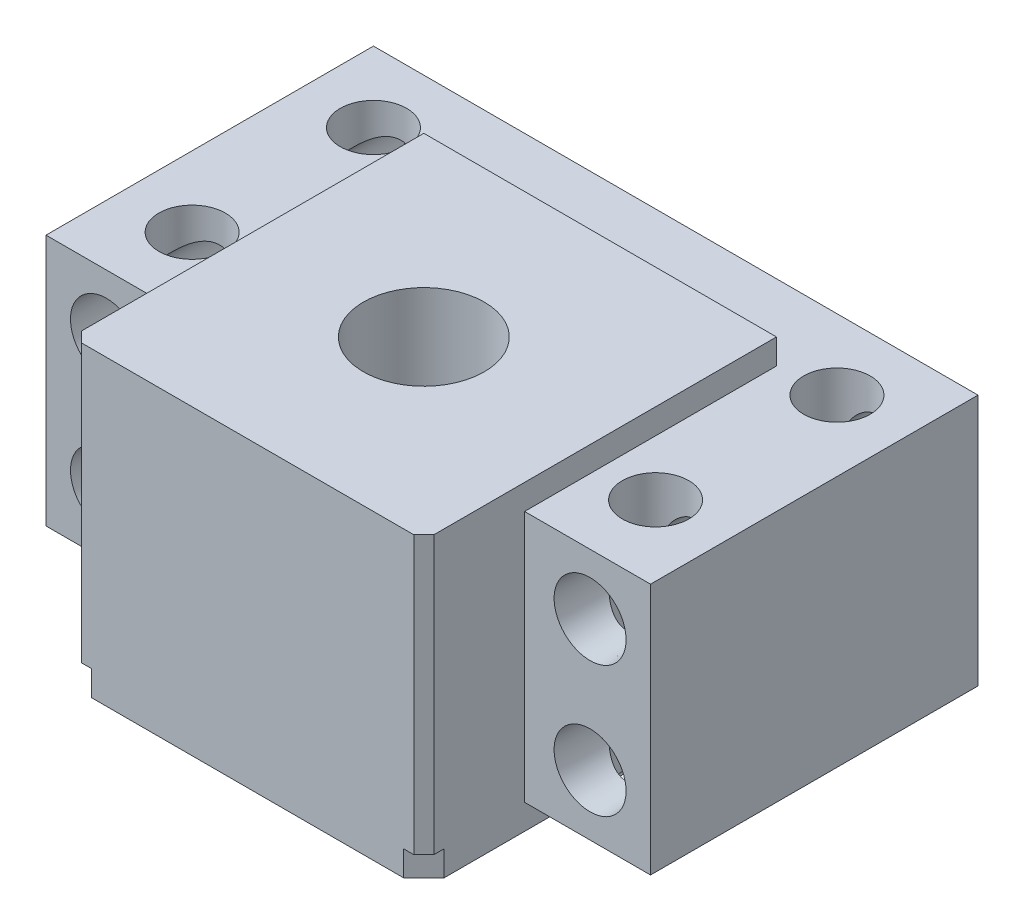
SolidWorks part; units mm, degrees
ref_plane "정면" through (0, 0, 0) normal (0, 0, 1) x (1, 0, 0)
ref_plane "윗면" through (0, 0, 0) normal (0, 1, 0) x (1, 0, 0)
ref_plane "우측면" through (0, 0, 0) normal (1, 0, 0) x (0, 0, -1)
sketch "스케치1" plane through (0, 0, 0) normal (0, 0, 1) x (1, 0, 0)
  line L1 (-30, 12.5) -> (30, 12.5)
  line L2 (-30, 12.5) -> (-30, -12.5)
  line L3 (-30, -12.5) -> (30, -12.5)
  line L4 (30, 12.5) -> (30, -12.5)
  line L5 (-30, 12.5) -> (30, -12.5) construction
  line L6 (-30, -12.5) -> (30, 12.5) construction
  point P0 (0, 0)
  dimension "D1" = 60
  dimension "D2" = 25
extrude "보스-돌출1" add sketch "스케치1" along normal blind 32.5
sketch "스케치2" plane through (0, -12.5, 0) normal (0, -1, 0) x (1, 0, 0)
  line L0 (-30, 0) -> (30, 0) construction
  circle A0 centre (-23, 25) radius 3.3002
  circle A1 centre (-23, 7) radius 3.3
  circle A2 centre (23, 25) radius 3.3002
  circle A3 centre (23, 7) radius 3.3002
  dimension "D1" = 6.6005
  dimension "D2" = 6.6
  dimension "D7" = 6.6005
  dimension "D8" = 6.6005
  dimension "D3" = 18
  dimension "D4" = 25
  dimension "D5" = 25
  dimension "D6" = 18
  dimension "D9" = 23
  dimension "D10" = 0
  dimension "D11" = 46
  dimension "D12" = 46
extrude "컷-돌출1" cut sketch "스케치2" against normal through all contours A1 | A3 | A2 | A0 region at (-23, -12.5, 7) region at (23, -12.5, 25) region at (23, -12.5, 7)
hole_wizard "1/16 Rc 나사 구멍1" positions "스케치3" profile "스케치4" size "1/16" standard "ISO"
sketch "스케치3" plane through (0, 0, 32.5) normal (0, 0, 1) x (1, 0, 0)
  line L0 (30, 12.5) -> (-30, 12.5) construction
  line L1 (-30, 12.5) -> (-30, -12.5) construction
  line L2 (-30, -12.5) -> (30, -12.5) construction
  line L3 (30, -12.5) -> (30, 12.5) construction
  point P0 (-24, 6.5)
  point P2 (-24, -6.5)
  point P4 (24, 6.5)
  point P6 (24, -6.5)
  dimension "D1" = 6
  dimension "D2" = 6
  dimension "D3" = 6
  dimension "D4" = 6
  dimension "D5" = 6
  dimension "D6" = 6
  dimension "D7" = 6
  dimension "D8" = 6
sketch "스케치4" plane through (-24, 6.5, 32.5) normal (1, 0, 0) x (0, -1, 0)
  line L0 (0, 0) -> (0, 41.8326)
  line L1 (3.05, 40) -> (0, 41.8326)
  line L2 (-3.05, 40) -> (0, 41.8326) construction
  line L3 (3.05, 40) -> (3.05, 7.4)
  line L4 (3.05, 7.4) -> (3.34, 7.4)
  line L5 (3.34, 7.4) -> (3.571, 0)
  line L6 (-3.34, 7.4) -> (-3.571, 0) construction
  line L7 (3.571, 0) -> (0, 0)
  line L8 (0, -6.35) -> (0, 107.95) construction
  line L11 (-3.05, 7.4) -> (-3.34, 7.4) construction
  dimension "탭 드릴 지름" = 6.1
  dimension "탭 드릴 깊이" = 40
  dimension "나사산 지름" = 7.142
  dimension "나사산 각도" = 3.576
  dimension "나사산 깊이" = 7.4
  dimension "드릴 각도" = 118
cosmetic thread "구멍 나사산1" parameters "D1"=7.4, "D2"=7.7227
cosmetic thread "구멍 나사산2" parameters "D1"=7.4, "D2"=7.7227
cosmetic thread "구멍 나사산3" parameters "D1"=7.4, "D2"=7.7227
cosmetic thread "구멍 나사산4" parameters "D1"=7.4, "D2"=7.7227
sketch "스케치5" plane through (0, -12.5, 0) normal (0, -1, 0) x (1, 0, 0)
  line L0 (-30, 0) -> (30, 0) construction
  line L1 (-17.5, 42.5) -> (17.5, 42.5)
  line L2 (-17.5, 42.5) -> (-17.5, 7.5)
  line L3 (-17.5, 7.5) -> (17.5, 7.5)
  line L4 (17.5, 42.5) -> (17.5, 7.5)
  line L5 (-17.5, 42.5) -> (17.5, 7.5) construction
  line L6 (-17.5, 7.5) -> (17.5, 42.5) construction
  point P0 (0, 25)
  dimension "D1" = 25
  dimension "D2" = 35
  dimension "D3" = 35
extrude "보스-돌출2" add sketch "스케치5" against normal blind 27.5
chamfer "모따기1" distance 1 angle 45 2 edges at (17.5, 1.25, 42.5) (-17.5, 1.25, 42.5)
extrude "보스-돌출3" add sketch "스케치5<2>" along normal blind 2.5
sketch "스케치5<2>" plane through (0, -12.5, 0) normal (0, -1, 0) x (1, 0, 0) same geometry as "스케치5"
chamfer "모따기2" distance 2 angle 45 2 edges at (-17.5, -13.75, 7.5) (17.5, -13.75, 7.5)
sketch "스케치6" plane through (0, -15, 0) normal (0, -1, 0) x (1, 0, 0)
  line L0 (-17.5, 40.5) -> (-15.5, 42.5)
  line L1 (-17.5, 42.5) -> (-17.5, 9.5) construction
  line L2 (17.5, 42.5) -> (-17.5, 42.5) construction
  line L3 (-15.5, 42.5) -> (-17.5, 42.5)
  line L4 (-17.5, 42.5) -> (-17.5, 40.5)
  line L5 (0, 42.5) -> (0, 7.5) construction
  line L6 (-15.5, 7.5) -> (15.5, 7.5) construction
  line L7 (17.5, 42.5) -> (17.5, 40.5)
  line L8 (15.5, 42.5) -> (17.5, 42.5)
  line L9 (17.5, 40.5) -> (15.5, 42.5)
  dimension "D1" = 2
  dimension "D2" = 2
extrude "컷-돌출2" cut sketch "스케치6" against normal up to vertex (2.5 mm away) up to point (-17.5, -12.5, 42.5)
sketch "스케치7" plane through (0, -15, 0) normal (0, -1, 0) x (1, 0, 0)
  line L0 (-15.5, 7.5) -> (15.5, 7.5) construction
  line L1 (-17.5, 32.5) -> (-17.5, 9.5) construction
  circle A0 centre (0, 25) radius 6
  dimension "D3" = 12
  dimension "D1" = 17.5
  dimension "D2" = 17.5
extrude "컷-돌출3" cut sketch "스케치7" against normal through all
equation "\"P\"=6.60047"
equation "\"N\"=17.1778"
